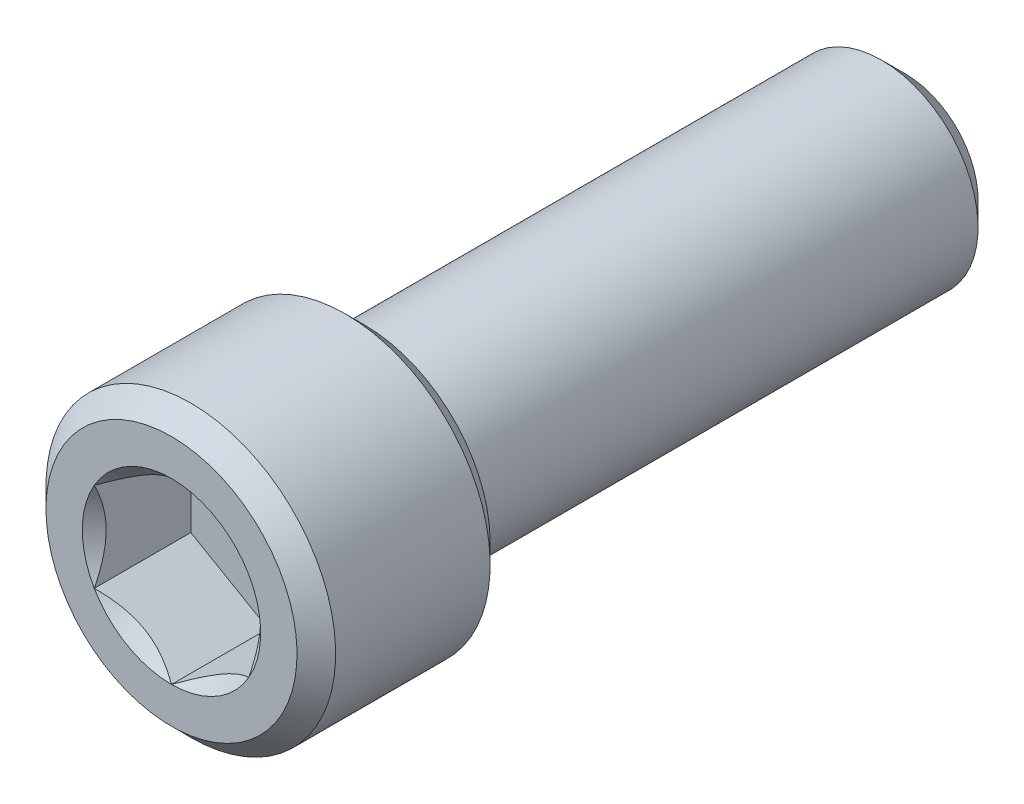
SolidWorks part; units mm, degrees
material "Alloy Steel"
ref_plane "Front Plane" through (0, 0, 0) normal (0, 0, 1) x (1, 0, 0)
ref_plane "Top Plane" through (0, 0, 0) normal (0, 1, 0) x (1, 0, 0)
ref_plane "Right Plane" through (0, 0, 0) normal (1, 0, 0) x (0, 0, -1)
sketch "Sketch1" plane through (0, 0, 0) normal (1, 0, 0) x (0, 0, -1)
  line L0 (15.0813, 0) -> (-15.0813, 0) construction
  line L1 (-15.0813, 0) -> (-15.0813, 5.1594)
  line L2 (-15.0813, 5.1594) -> (-14.2875, 5.9531)
  line L3 (-14.2875, 5.9531) -> (-7.9375, 5.9531)
  line L4 (-7.9375, 5.9531) -> (-7.1437, 5.1594)
  line L5 (-7.1437, 5.1594) -> (-7.1437, 3.9751)
  line L6 (-7.1437, 3.9751) -> (14.0935, 3.9751)
  line L7 (14.0935, 3.9751) -> (15.0812, 2.9873)
  line L8 (15.0812, 2.9873) -> (15.0813, 0)
  line L9 (14.9931, 4.1279) -> (16.4042, 4.1279) construction
  line L10 (16.4042, 4.1279) -> (15.6986, 2.9058) construction
  line L11 (15.6986, 2.9058) -> (14.9931, 4.1279) construction
  line L12 (15.0812, 3.9751) -> (16.316, 3.9751) construction
  line L13 (15.6986, 4.1279) -> (15.6986, 3.9751) construction
  line L14 (15.6104, 3.0586) -> (15.7868, 3.0586) construction
  line L15 (15.6986, 3.0586) -> (15.6986, 2.9058) construction
  line L16 (15.0372, 4.0515) -> (16.3601, 4.0515)
  line L17 (16.3601, 4.0515) -> (15.7868, 3.0586)
  line L18 (15.7868, 3.0586) -> (15.6104, 3.0586)
  line L19 (15.6104, 3.0586) -> (15.0372, 4.0515)
  line L20 (14.0935, -3.9751) -> (11.5535, -3.9751) construction
  point P4 (0, 0)
  point P25 (15.6986, 4.0515)
  point P26 (15.0812, 3.9751)
  point P33 (11.5535, -3.9751)
  dimension "Head Ht" = 7.9375
  dimension "Screw Size" = 7.9502
  dimension "Head Dia" = 11.9062
  dimension "D1" = 45
  dimension "D2" = 45
  dimension "D3" = 0.7937
  dimension "D4" = 0.7937
  dimension "Pitch" = 1.4111
  dimension "D5" = 0.1764
  dimension "D6" = 0.9878
  dimension "D7" = 2.54
  dimension "Length" = 22.225
sketch "Sketch2" plane through (0, 0, 0) normal (0, 0, 1) x (1, 0, 0)
  line L1 (0, 3.6662) -> (-3.175, 1.8331)
  line L2 (-3.175, 1.8331) -> (-3.175, -1.8331)
  line L3 (-3.175, -1.8331) -> (0, -3.6662)
  line L4 (0, -3.6662) -> (3.175, -1.8331)
  line L5 (3.175, -1.8331) -> (3.175, 1.8331)
  line L6 (3.175, 1.8331) -> (0, 3.6662)
  circle A0 centre (0, 0) radius 3.175 construction
  circle A1 centre (0, 0) radius 5.9531
  point P1 (0, 5.9531)
  dimension "D1" = 11.9062
  dimension "Drive Size" = 6.35
sketch "Sketch3" plane through (0, 0, 0) normal (1, 0, 0) x (0, 0, -1)
  line L0 (15.0813, 0) -> (-15.0813, 0) construction
  line L1 (-15.0813, 0) -> (-15.0813, 5.1594) construction
  line L2 (-15.0813, 5.1594) -> (-14.2875, 5.9531) construction
  line L3 (-14.2875, 5.9531) -> (-7.9375, 5.9531) construction
  line L4 (-7.9375, 5.9531) -> (-7.1437, 5.1594) construction
  line L5 (-7.1437, 5.1594) -> (-7.1437, 3.9751) construction
  line L6 (-7.1437, 3.9751) -> (14.0935, 3.9751) construction
  line L7 (14.0935, 3.9751) -> (15.0812, 2.9873) construction
  line L8 (15.0812, 2.9873) -> (15.0813, 0) construction
  line L9 (15.0813, 0) -> (-15.0813, 0)
  line L10 (-15.0813, 0) -> (-15.0813, 5.1594)
  line L11 (-15.0813, 5.1594) -> (-14.2875, 5.9531)
  line L12 (-14.2875, 5.9531) -> (-7.9375, 5.9531)
  line L13 (-7.9375, 5.9531) -> (-7.1437, 5.1594)
  line L14 (-7.1437, 5.1594) -> (-7.1437, 3.9751)
  line L15 (-7.1437, 3.9751) -> (14.0935, 3.9751)
  line L16 (14.0935, 3.9751) -> (15.0812, 2.9873)
  line L17 (15.0812, 2.9873) -> (15.0813, 0)
revolve "Revolve1" add sketch "Sketch3" angle 360 about L0
sketch "Sketch4" plane through (0, 0, 15.0813) normal (0, 0, 1) x (1, 0, 0)
  line L0 (0, -3.6662) -> (3.175, -1.8331) construction
  line L1 (3.175, -1.8331) -> (3.175, 1.8331) construction
  line L2 (3.175, 1.8331) -> (0, 3.6662) construction
  line L3 (0, 3.6662) -> (-3.175, 1.8331) construction
  line L4 (-3.175, 1.8331) -> (-3.175, -1.8331) construction
  line L5 (-3.175, -1.8331) -> (0, -3.6662) construction
  line L6 (0, -3.6662) -> (3.175, -1.8331)
  line L7 (3.175, -1.8331) -> (3.175, 1.8331)
  line L8 (3.175, 1.8331) -> (0, 3.6662)
  line L9 (0, 3.6662) -> (-3.175, 1.8331)
  line L10 (-3.175, 1.8331) -> (-3.175, -1.8331)
  line L11 (-3.175, -1.8331) -> (0, -3.6662)
extrude "Cut-Extrude1" cut sketch "Sketch4" against normal blind 3.9688
sketch "Sketch5" plane through (0, 0, 15.0813) normal (0, 0, 1) x (1, 0, 0)
  circle A0 centre (0, 0) radius 3.6662
extrude "Cut-Extrude3" cut sketch "Sketch5" against normal through all draft 45
split "Split1" [suppressed] bodies to split 107
sketch "Sketch6" [suppressed] plane through (0, 0, -15.0812) normal (0, 0, -1) x (-1, 0, 0)
  circle A0 centre (0, 0) radius 3.9751 construction
  circle A1 centre (0, 0) radius 3.9751
curve "Helix/Spiral1" [suppressed] pitch 1.4111 height 23.6361 turns 16.75
sketch "Sketch7" [suppressed] plane through (0, 0, 0) normal (1, 0, 0) x (0, 0, -1)
  line L0 (15.0372, 4.0515) -> (16.3601, 4.0515) construction
  line L1 (16.3601, 4.0515) -> (15.7868, 3.0586) construction
  line L2 (15.7868, 3.0586) -> (15.6104, 3.0586) construction
  line L3 (15.6104, 3.0586) -> (15.0372, 4.0515) construction
  line L4 (15.0372, 4.0515) -> (16.3601, 4.0515)
  line L5 (16.3601, 4.0515) -> (15.7868, 3.0586)
  line L6 (15.7868, 3.0586) -> (15.6104, 3.0586)
  line L7 (15.6104, 3.0586) -> (15.0372, 4.0515)
sweep "Cut-Sweep1" [suppressed] cut profiles "Sketch7" path "Helix/Spiral1"
sketch "Sketch8" [suppressed] plane through (0, 0, 7.1438) normal (0, 0, -1) x (-1, 0, 0)
  circle A1 centre (0, 0) radius 3.9751
extrude "Boss-Extrude1" [suppressed] add sketch "Sketch8" along normal up to next draft 20
equation "\"D3@Sketch1\"=\"Head Ht@Sketch1\"/10"
equation "\"D4@Sketch1\"=\"Head Ht@Sketch1\"/10"
equation "\"D5@Sketch1\"=\"Pitch@Sketch1\"/8"
equation "\"D6@Sketch1\"=\"Pitch@Sketch1\"*.7"
equation "\"D7@Sketch1\"=\"Pitch@Sketch1\"*2.5-\"D6@Sketch1\""
equation "\"D1@Cut-Extrude1\"=\"Head Ht@Sketch1\"/2"
equation "\"D4@Helix/Spiral1\"=\"Pitch@Sketch1\""
equation "\"D3@Helix/Spiral1\"=\"Length@Sketch1\"+\"D4@Helix/Spiral1\""
